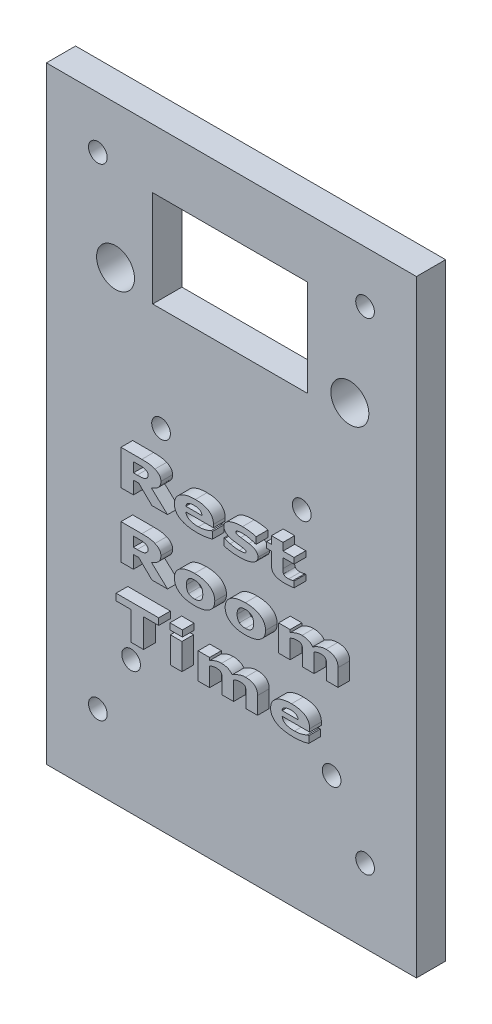
SolidWorks part; units mm, degrees
ref_plane "Piano frontale" through (0, 0, 0) normal (0, 0, 1) x (1, 0, 0)
ref_plane "Piano superiore" through (0, 0, 0) normal (0, 1, 0) x (1, 0, 0)
ref_plane "Piano destro" through (0, 0, 0) normal (1, 0, 0) x (0, 0, -1)
sketch "Schizzo1" plane through (0, 0, 0) normal (0, 0, 1) x (1, 0, 0)
  line L0 (77.34, 47.98) -> (77.34, -56)
  line L5 (58.6997, 37.8376) -> (32.1997, 37.8376)
  line L6 (58.6997, 37.8376) -> (58.6997, 21.3376)
  line L7 (58.6997, 21.3376) -> (32.1997, 21.3376)
  line L8 (32.1997, 37.8376) -> (32.1997, 21.3376)
  line L9 (77.34, -56) -> (14, -56)
  line L10 (14, 47.98) -> (14, -56)
  line L11 (77.34, 47.98) -> (14, 47.98)
  circle A0 centre (68.5477, 39.1333) radius 1.6
  circle A1 centre (22.8135, 39.1333) radius 1.6
  circle A2 centre (68.5477, -43.3771) radius 1.6
  circle A3 centre (22.8135, -43.3771) radius 1.6
  circle A4 centre (57.7111, 3.5977) radius 1.6
  circle A5 centre (33.6306, 3.5977) radius 1.6
  circle A6 centre (62.83, -33.235) radius 1.6
  circle A7 centre (28.5042, -33.235) radius 1.6
  circle A8 centre (65.9441, 23.5591) radius 3.25
  circle A9 centre (25.8413, 23.5591) radius 3.25
  dimension "D1" = 3.2
  dimension "D2" = 6.5
  dimension "D3" = 3.2
  dimension "D4" = 16.5
  dimension "D5" = 26.5
extrude "Estrusione-Estrusione1" add sketch "Schizzo1" along normal blind 5
hole_wizard "Foro svasato per Vite M3-1" positions "Schizzo3D1" profile "Schizzo2" countersink size "M3" standard "Ansi Metric" rebuild error yes end condition through all
sketch3d "Schizzo3D1"
  line L0 (22.8135, 39.1333, 5) -> (22.8135, 39.1333, 0) construction
  line L1 (68.5477, 39.1333, 5) -> (68.5477, 39.1333, 0) construction
  line L2 (68.5477, -43.3771, 5) -> (68.5477, -43.3771, 0) construction
  line L3 (22.8135, -43.3771, 5) -> (22.8135, -43.3771, 0) construction
  point P0 (22.8135, 39.1333, 5)
  point P4 (68.5477, 39.1333, 5)
  point P8 (68.5477, -43.3771, 5)
  point P12 (22.8135, -43.3771, 5)
sketch "Schizzo2" plane through (22.8135, 39.1333, 5) normal (1, 0, 0) x (0, -1, 0)
  line L0 (0, 0) -> (0, 5)
  line L1 (0, 5) -> (1.7, 5)
  line L2 (1.7, 5) -> (1.7, 1.45)
  line L3 (1.7, 1.45) -> (3.15, 0)
  line L5 (3.15, 0) -> (0, 0)
  line L6 (-1.7, 1.45) -> (-3.15, 0) construction
  line L11 (0, -6.35) -> (0, 107.95) construction
  dimension "Thru Hole Dia." = 3.4
  dimension "Thru Hole Depth" = 5
  dimension "Near C'Sink Dia." = 6.3
  dimension "Near C'Sink Angle" = 90
hole_wizard "Foro svasato per Vite M3-2" positions "Schizzo3D2" profile "Schizzo3" countersink size "M3" standard "Ansi Metric" rebuild error yes end condition through all
sketch3d "Schizzo3D2"
  line L0 (33.6306, 3.5977, 5) -> (33.6306, 3.5977, 0) construction
  line L1 (57.7111, 3.5977, 5) -> (57.7111, 3.5977, 0) construction
  line L2 (62.83, -33.235, 5) -> (62.83, -33.235, 0) construction
  line L3 (28.5042, -33.235, 5) -> (28.5042, -33.235, 0) construction
  point P0 (33.6306, 3.5977, 5)
  point P4 (57.7111, 3.5977, 5)
  point P8 (62.83, -33.235, 5)
  point P12 (28.5042, -33.235, 5)
sketch "Schizzo3" plane through (33.6306, 3.5977, 5) normal (1, 0, 0) x (0, -1, 0)
  line L0 (0, 0) -> (0, 5)
  line L1 (0, 5) -> (1.7, 5)
  line L2 (1.7, 5) -> (1.7, 1.45)
  line L3 (1.7, 1.45) -> (3.15, 0)
  line L5 (3.15, 0) -> (0, 0)
  line L6 (-1.7, 1.45) -> (-3.15, 0) construction
  line L11 (0, -6.35) -> (0, 107.95) construction
  dimension "Thru Hole Dia." = 3.4
  dimension "Thru Hole Depth" = 5
  dimension "Near C'Sink Dia." = 6.3
  dimension "Near C'Sink Angle" = 90
sketch "Schizzo4" plane through (0, 0, 5) normal (0, 0, 1) x (1, 0, 0)
  text T0 "Rest\r\nRoom\r\nTime" font "Verdana" height 6
extrude "Estrusione-Estrusione2" add sketch "Schizzo4" along normal blind 2
sketch "Schizzo5" plane through (0, 0, 0) normal (0, 0, -1) x (-1, 0, 0)
  line L0 (-69.84, 40.48) -> (-69.84, -48.5)
  line L1 (-72.34, 42.98) -> (-19, 42.98)
  line L2 (-72.34, 42.98) -> (-72.34, -51)
  line L3 (-72.34, -51) -> (-19, -51)
  line L4 (-19, 42.98) -> (-19, -51)
  line L5 (-69.84, -48.5) -> (-21.5, -48.5)
  line L6 (-21.5, 40.48) -> (-21.5, -48.5)
  line L7 (-69.84, 40.48) -> (-21.5, 40.48)
  dimension "D1" = 2.5
extrude "Taglio-Estrusione1" cut sketch "Schizzo5" against normal blind 2
